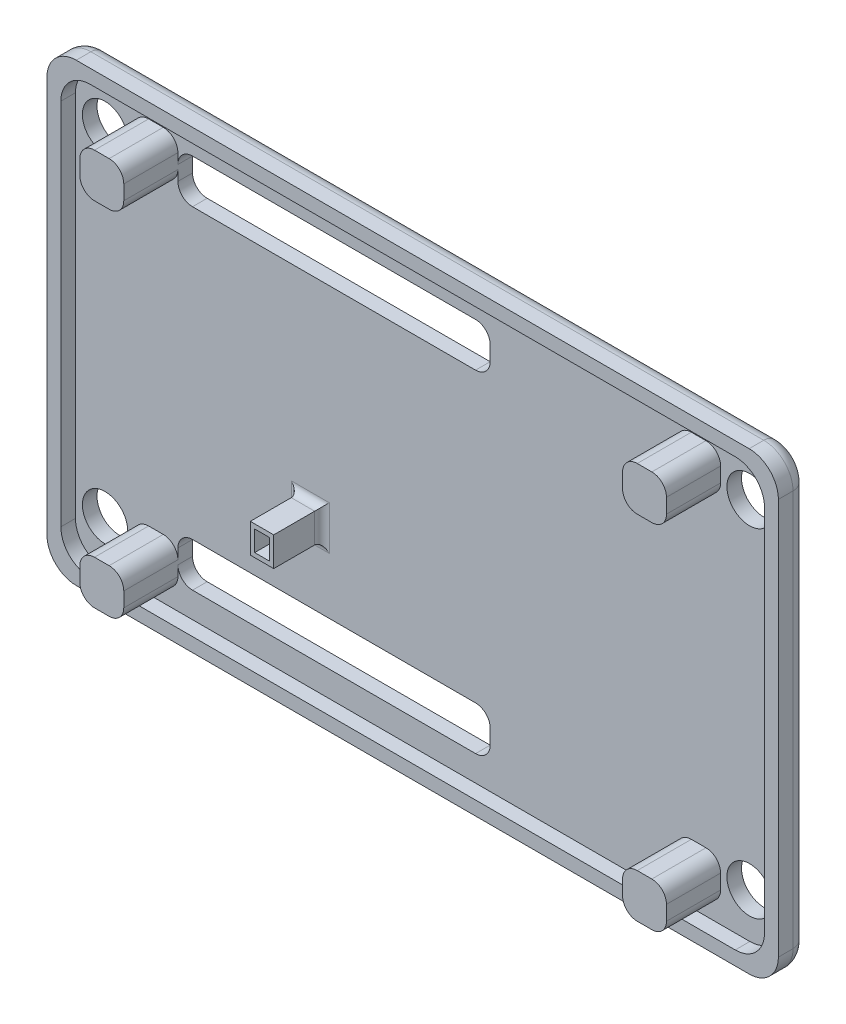
SolidWorks part; units mm, degrees
material "ABS"
ref_plane "Front" through (0, 0, 0) normal (0, 0, 1) x (1, 0, 0)
ref_plane "Top" through (0, 0, 0) normal (0, 1, 0) x (1, 0, 0)
ref_plane "Right" through (0, 0, 0) normal (1, 0, 0) x (0, 0, -1)
sketch "Sketch1" plane through (0, 0, 0) normal (0, 0, 1) x (1, 0, 0)
  line L1 (-25, -15.55) -> (25, -15.55)
  line L2 (-25, -15.55) -> (-25, 15.55)
  line L3 (-25, 15.55) -> (25, 15.55)
  line L4 (25, -15.55) -> (25, 15.55)
  line L5 (-25, -15.55) -> (25, 15.55) construction
  line L6 (-25, 15.55) -> (25, -15.55) construction
  point P0 (0, 0)
  dimension "D1" = 50
  dimension "D2" = 31.1
extrude "Boss-Extrude1" add sketch "Sketch1" along normal blind 1
sketch "Sketch2" plane through (0, 0, 1) normal (0, 0, 1) x (1, 0, 0)
  line L1 (-25, -15.55) -> (25, -15.55)
  line L2 (-25, -15.55) -> (-25, 15.55)
  line L3 (-25, 15.55) -> (25, 15.55)
  line L4 (25, -15.55) -> (25, 15.55)
  line L5 (-25, -15.55) -> (25, 15.55) construction
  line L6 (-25, 15.55) -> (25, -15.55) construction
  line L7 (-24.05, -14.6) -> (24.05, -14.6)
  line L8 (-24.05, -14.6) -> (-24.05, 14.6)
  line L9 (-24.05, 14.6) -> (24.05, 14.6)
  line L10 (24.05, -14.6) -> (24.05, 14.6)
  line L11 (-24.05, -14.6) -> (24.05, 14.6) construction
  line L12 (-24.05, 14.6) -> (24.05, -14.6) construction
  point P0 (0, 0)
  point P5 (0, 0)
  dimension "D1" = 0.95
  dimension "D2" = 0.95
extrude "Boss-Extrude2" add sketch "Sketch2" along normal blind 1
sketch "Sketch3" plane through (0, 0, 1) normal (0, 0, 1) x (1, 0, 0)
  line L0 (-24.05, 0) -> (24.05, 0) construction
  line L1 (-24.05, 14.6) -> (-20.05, 14.6) construction
  line L2 (-24.05, 14.6) -> (-24.05, 9.6) construction
  line L3 (-24.05, 9.6) -> (-20.05, 9.6) construction
  line L4 (-20.05, 14.6) -> (-20.05, 9.6) construction
  line L5 (-24.05, 14.6) -> (-24.05, -14.6) construction
  line L6 (24.05, -14.6) -> (24.05, 14.6) construction
  line L7 (0, 14.6) -> (0, -14.6) construction
  line L8 (24.05, 14.6) -> (-24.05, 14.6) construction
  line L9 (-24.05, -14.6) -> (24.05, -14.6) construction
  line L26 (20.05, 10.55) -> (17.05, 10.55)
  line L27 (-20.05, 13.55) -> (-17.05, 13.55)
  line L28 (-20.05, 13.55) -> (-20.05, 10.55)
  line L29 (-20.05, 10.55) -> (-17.05, 10.55)
  line L30 (-17.05, 13.55) -> (-17.05, 10.55)
  line L31 (17.05, 13.55) -> (17.05, 10.55)
  line L32 (20.05, 13.55) -> (17.05, 13.55)
  line L33 (20.05, 13.55) -> (20.05, 10.55)
  line L34 (20.05, -13.55) -> (20.05, -10.55)
  line L35 (20.05, -13.55) -> (17.05, -13.55)
  line L36 (17.05, -13.55) -> (17.05, -10.55)
  line L37 (20.05, -10.55) -> (17.05, -10.55)
  line L38 (-20.05, -10.55) -> (-17.05, -10.55)
  line L39 (-17.05, -13.55) -> (-17.05, -10.55)
  line L40 (-20.05, -13.55) -> (-17.05, -13.55)
  line L41 (-20.05, -13.55) -> (-20.05, -10.55)
  dimension "D1" = 5
  dimension "D2" = 4
  dimension "D3" = 3
  dimension "D4" = 3
  dimension "D5" = 1.05
extrude "Boss-Extrude3" add sketch "Sketch3" along normal blind 3.7
sketch "Sketch4" plane through (0, 0, 1) normal (0, 0, 1) x (1, 0, 0)
  line L0 (0, 11.55) -> (0, -11.55) construction
  line L1 (-22.03, -11.55) -> (22.03, -11.55) construction
  line L2 (-22.03, -11.55) -> (-22.03, 11.55) construction
  line L3 (-22.03, 11.55) -> (22.03, 11.55) construction
  line L4 (22.03, -11.55) -> (22.03, 11.55) construction
  line L5 (-22.03, -11.55) -> (22.03, 11.55) construction
  line L6 (-22.03, 11.55) -> (22.03, -11.55) construction
  line L7 (-22.03, 0) -> (22.03, 0) construction
  circle A0 centre (-22.03, 11.55) radius 1.55
  circle A1 centre (22.03, 11.55) radius 1.55
  circle A2 centre (-22.03, -11.55) radius 1.55
  circle A3 centre (22.03, -11.55) radius 1.55
  point P0 (0, 0)
  dimension "D1" = 44.06
  dimension "D3" = 3.1
  dimension "D2" = 23.1
extrude "Cut-Extrude1" cut sketch "Sketch4" against normal up to surface (1 mm away) up to face at (0, 0, 0)
sketch "Sketch5" plane through (0, 0, 1) normal (0, 0, 1) x (1, 0, 0)
  line L1 (4.3, 12.85) -> (-17.05, 12.85)
  line L2 (4.3, 12.85) -> (4.3, 9.85)
  line L3 (4.3, 9.85) -> (-17.05, 9.85)
  line L4 (-17.05, 12.85) -> (-17.05, 9.85)
  line L7 (24.05, 14.6) -> (-24.05, 14.6) construction
  line L8 (-17.05, 10.55) -> (-17.05, 13.55) construction
  line L9 (-25, 0) -> (25, 0) construction
  line L10 (-25, 15.55) -> (-25, -15.55) construction
  line L11 (25, -15.55) -> (25, 15.55) construction
  line L12 (4.3, -9.85) -> (-17.05, -9.85)
  line L13 (-17.05, -12.85) -> (-17.05, -9.85)
  line L14 (4.3, -12.85) -> (-17.05, -12.85)
  line L15 (4.3, -12.85) -> (4.3, -9.85)
  line L16 (-25, -15.55) -> (25, -15.55) construction
  line L17 (-8.5, -3.8) -> (-7.5, -3.8)
  line L18 (-8.5, -3.8) -> (-8.5, -5.2)
  line L19 (-8.5, -5.2) -> (-7.5, -5.2)
  line L20 (-7.5, -3.8) -> (-7.5, -5.2)
  dimension "D1" = 3
  dimension "D2" = 21.35
  dimension "D3" = 16.5
  dimension "D4" = 1.75
  dimension "D5" = 10.35
  dimension "D6" = 1.4
  dimension "D7" = 1
extrude "Cut-Extrude2" cut sketch "Sketch5" against normal up to surface (1 mm away) up to face at (20.48, 11.55, 0)
sketch "Sketch6" plane through (0, 0, 1) normal (0, 0, 1) x (1, 0, 0)
  line L0 (-8, -3.8) -> (-8, -5.2) construction
  line L1 (-7.5, -3.8) -> (-8.5, -3.8) construction
  line L2 (-8.5, -5.2) -> (-7.5, -5.2) construction
  line L4 (-8.8, -5.5) -> (-7.2, -5.5)
  line L5 (-8.8, -5.5) -> (-8.8, -3.5)
  line L6 (-8.8, -3.5) -> (-7.2, -3.5)
  line L7 (-7.2, -5.5) -> (-7.2, -3.5)
  line L8 (-8.8, -5.5) -> (-7.2, -3.5) construction
  line L9 (-8.8, -3.5) -> (-7.2, -5.5) construction
  line L10 (-8.5, -5.2) -> (-7.5, -5.2)
  line L11 (-8.5, -5.2) -> (-8.5, -3.8)
  line L12 (-8.5, -3.8) -> (-7.5, -3.8)
  line L13 (-7.5, -5.2) -> (-7.5, -3.8)
  line L14 (-8.5, -5.2) -> (-7.5, -3.8) construction
  line L15 (-8.5, -3.8) -> (-7.5, -5.2) construction
  point P6 (-8, -4.5)
  point P11 (-8, -4.5)
  dimension "D1" = 0.3
  dimension "D2" = 0.3
extrude "Boss-Extrude4" add sketch "Sketch6" along normal blind 3.3
fillet "Fillet1" radius 2 8 edges at (24.05, 14.6, 1.5) (-24.05, 14.6, 1.5) (-24.05, -14.6, 1.5) (24.05, -14.6, 1.5) (25, -15.55, 1) (-25, -15.55, 1) (25, 15.55, 1) (-25, 15.55, 1)
fillet "Fillet2" radius 1 16 edges at (-20.05, -13.55, 2.85) (-17.05, -13.55, 2.85) (-17.05, -10.55, 2.85) (-20.05, -10.55, 2.85) (20.05, 13.55, 2.85) (17.05, 13.55, 2.85) (17.05, 10.55, 2.85) (20.05, 10.55, 2.85) (-20.05, 10.55, 2.85) (-17.05, 10.55, 2.85) (-17.05, 13.55, 2.85) (20.05, -13.55, 2.85) (20.05, -10.55, 2.85) (17.05, -10.55, 2.85) (17.05, -13.55, 2.85) (-20.05, 13.55, 2.85)
fillet "Fillet3" radius 1 8 edges at (24.4142, 14.9642, 0) (25, 0, 0) (24.4142, -14.9642, 0) (0, -15.55, 0) (-24.4142, -14.9642, 0) (-25, 0, 0) (-24.4142, 14.9642, 0) (0, 15.55, 0)
fillet "Fillet4" radius 1 8 edges at (4.3, -9.85, 0.5) (4.3, -12.85, 0.5) (-17.0961, -12.85, 0.5) (-17.05, -9.85, 0.5) (4.3, 12.85, 0.5) (4.3, 9.85, 0.5) (-17.0961, 12.85, 0.5) (-17.05, 9.85, 0.5)
fillet "Fillet5" radius 0.5 4 edges at (-8, -3.5, 1) (-8, -5.5, 1) (-7.2, -4.5, 1) (-8.8, -4.5, 1)
fillet "Fillet6" radius 0.5 4 edges at (-7.5, -4.5, 0) (-8, -5.2, 0) (-8.5, -4.5, 0) (-8, -3.8, 0)
